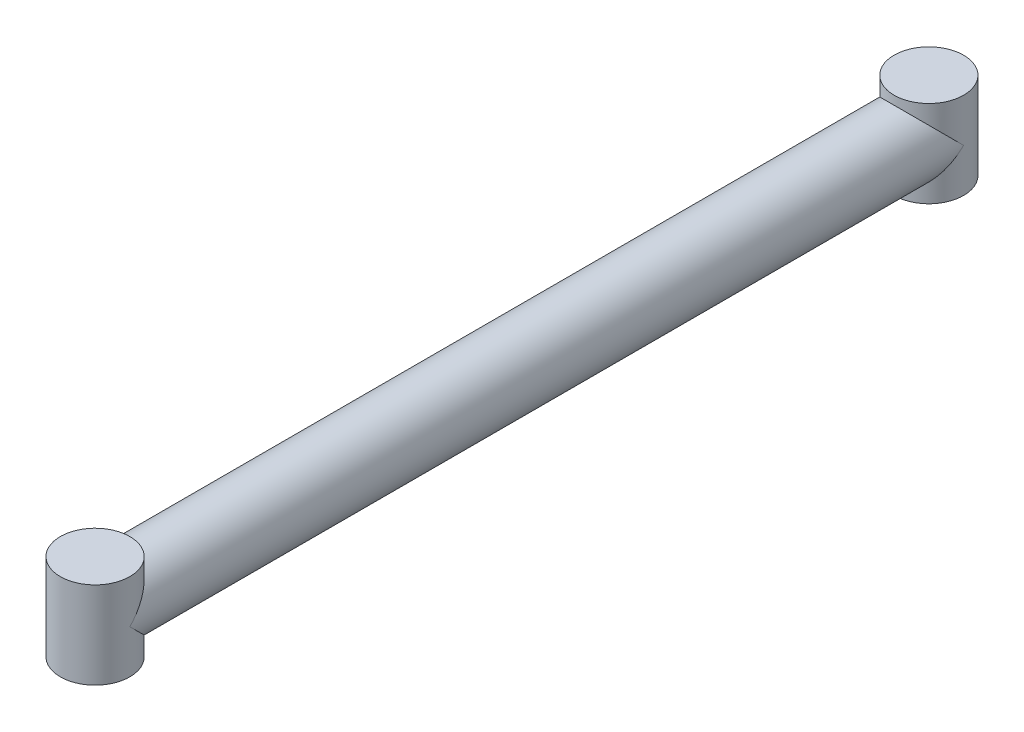
SolidWorks part; units mm, degrees
ref_plane "Alzado" through (0, 0, 0) normal (0, 0, 1) x (1, 0, 0)
ref_plane "Planta" through (0, 0, 0) normal (0, 1, 0) x (1, 0, 0)
ref_plane "Vista lateral" through (0, 0, 0) normal (1, 0, 0) x (0, 0, -1)
sketch "Croquis1" plane through (0, 0, 0) normal (0, 0, 1) x (1, 0, 0)
  circle A0 centre (0, 0) radius 10
  dimension "D1" = 20
extrude "Saliente-Extruir1" add sketch "Croquis1" along normal blind 240
sketch "Croquis2" plane through (0, 0, 0) normal (0, 1, 0) x (1, 0, 0)
  line L0 (-10, -240) -> (10, -240) construction
  circle A0 centre (0, 0) radius 10
  circle A1 centre (0, -240) radius 10
extrude "Saliente-Extruir2" add sketch "Croquis2" against normal blind 12.5 and the other way blind 12.5
